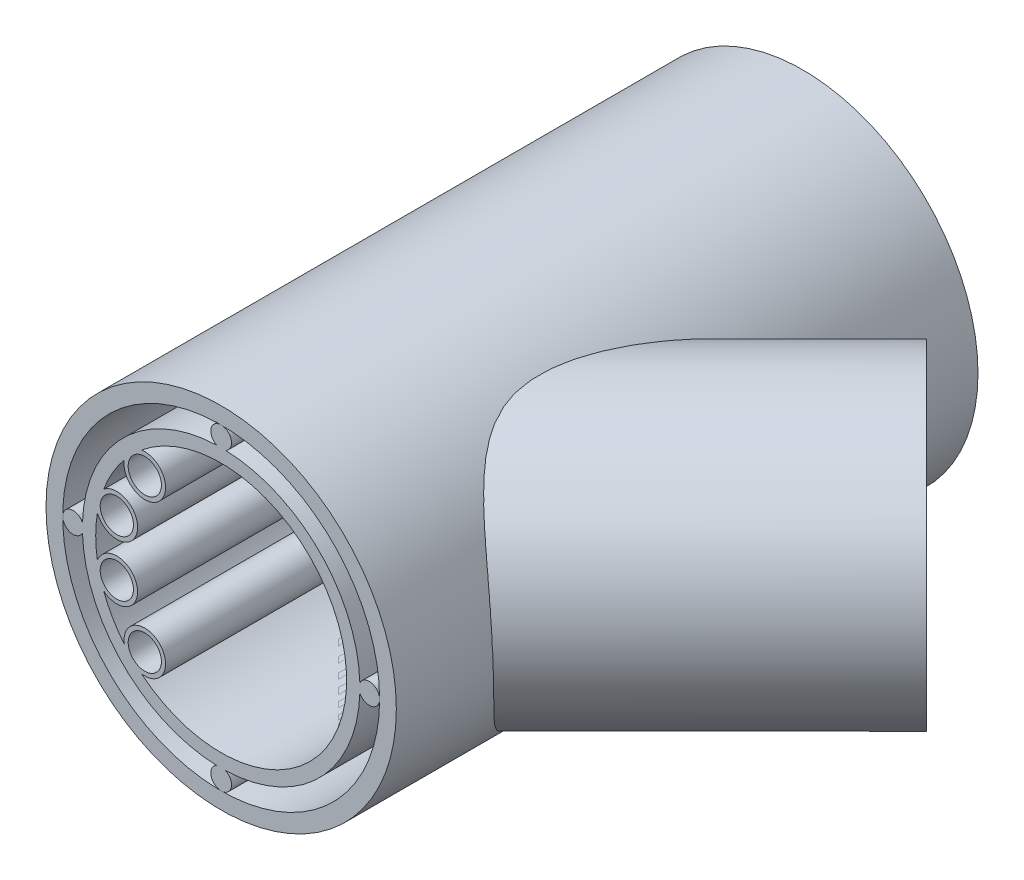
SolidWorks part; units mm, degrees
ref_plane "Front Plane" through (0, 0, 0) normal (0, 0, 1) x (1, 0, 0)
ref_plane "Top Plane" through (0, 0, 0) normal (0, 1, 0) x (1, 0, 0)
ref_plane "Right Plane" through (0, 0, 0) normal (1, 0, 0) x (0, 0, -1)
sketch "Sketch1" plane through (0, 0, 0) normal (0, 0, 1) x (1, 0, 0)
  circle A0 centre (0, 0) radius 21.08
  circle A1 centre (0, 0) radius 19.07
  dimension "D1" = 42.16
  dimension "D2" = 2.01
  dimension "D3" = 38.14
extrude "Boss-Extrude1" add sketch "Sketch1" against normal blind 70
sketch "Sketch3" plane through (0, 0, 0) normal (0, 0, 1) x (1, 0, 0)
  circle A0 centre (0, 0) radius 16.7
  circle A1 centre (0, 0) radius 15.1
  dimension "D1" = 33.4
  dimension "D2" = 1.6
extrude "Boss-Extrude2" add sketch "Sketch3" against normal blind 70 separate body
sketch "Sketch4" plane through (0, 0, 0) normal (0, 0, 1) x (1, 0, 0)
  circle A0 centre (0, -17.82) radius 1.25
  circle A6 centre (-17.82, 0) radius 1.25
  circle A7 centre (0, 17.82) radius 1.25
  circle A8 centre (17.82, 0) radius 1.25
  point P12 (0, 0)
  dimension "D1" = 4
  dimension "D4" = 2.5
  dimension "D5" = 17.82
extrude "Boss-Extrude3" add sketch "Sketch4" against normal blind 70
ref_plane "Plane1" through (0, 0, 0) normal (0.7071, 0, -0.7071) x (-0.7071, 0, -0.7071)
ref_plane "Plane2" through (45.9619, 0, -45.9619) normal (0.7071, 0, -0.7071) x (-0.7071, 0, -0.7071)
sketch "Sketch5" plane through (45.9619, 0, -45.9619) normal (0.7071, 0, -0.7071) x (-0.7071, 0, -0.7071)
  circle A0 centre (9.9856, 0.5373) radius 16.7
  circle A1 centre (9.9856, 0.5373) radius 15.1
  dimension "D1" = 33.4
  dimension "D2" = 1.6
  dimension "D3" = 10
extrude "Boss-Extrude8" add sketch "Sketch5" against normal blind 50 from offset 5 separate body offset against normal yes
sketch "Sketch6" plane through (0, 0, 0) normal (0, 0, 1) x (1, 0, 0)
  circle A0 centre (0, 0) radius 15.1 construction
  circle A1 centre (0, 0) radius 15.1
extrude "Cut-Extrude1" cut sketch "Sketch6" against normal through all from offset 20
sketch "Sketch7" plane through (-82.0711, 0, -173.9949) normal (-0.7071, 0, 0.7071) x (0.7071, 0, 0.7071)
  circle A0 centre (171.0805, 0.5373) radius 15.1 construction
  circle A1 centre (171.0805, 0.5373) radius 15.1
sketch "Sketch8" plane through (0, 0, 0) normal (0, 0, 1) x (1, 0, 0)
  circle A0 centre (0, 0) radius 15.1 construction
  circle A1 centre (0, 0) radius 15.1
  circle A2 centre (-9.1924, -9.1924) radius 2.5
  circle A3 centre (-9.1924, -9.1924) radius 2
  circle A4 centre (-12.557, -3.3646) radius 2
  circle A5 centre (-12.557, -3.3646) radius 2.5
  circle A6 centre (-12.557, 3.3646) radius 2
  circle A7 centre (-12.557, 3.3646) radius 2.5
  circle A8 centre (-9.1924, 9.1924) radius 2
  circle A9 centre (-9.1924, 9.1924) radius 2.5
  point P20 (0, 0)
  dimension "D1" = 5
  dimension "D2" = 13
  dimension "D3" = 0.5
  dimension "D4" = 4
extrude "Cut-Extrude3" cut sketch "Sketch7" along normal blind 50
extrude "Boss-Extrude9" add sketch "Sketch8" against normal through all contours A5 | A4 | A3 | A2 | A6 | A7 | A8 | A9
